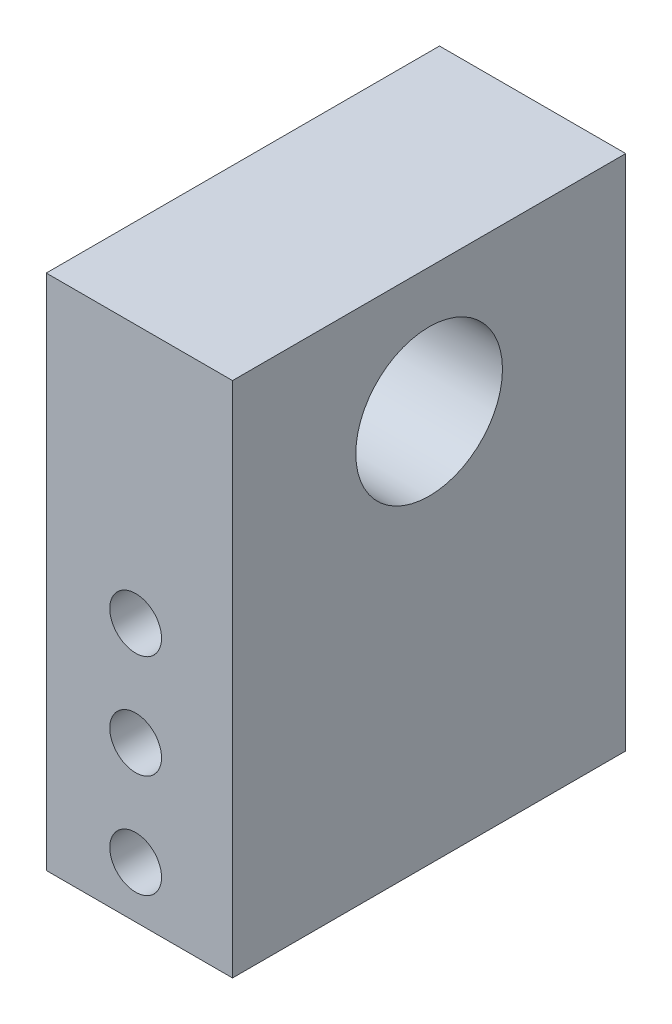
SolidWorks part; units mm, degrees
ref_plane "Front Plane" through (0, 0, 0) normal (0, 0, 1) x (1, 0, 0)
ref_plane "Top Plane" through (0, 0, 0) normal (0, 1, 0) x (1, 0, 0)
ref_plane "Right Plane" through (0, 0, 0) normal (1, 0, 0) x (0, 0, -1)
sketch "Sketch1" plane through (0, 0, 0) normal (0, 0, 1) x (1, 0, 0)
  line L1 (0, 0) -> (45.72, 0)
  line L2 (0, 0) -> (0, 76.2)
  line L3 (0, 76.2) -> (45.72, 76.2)
  line L4 (45.72, 0) -> (45.72, 76.2)
  dimension "D1" = 76.2
  dimension "D2" = 45.72
extrude "Boss-Extrude1" add sketch "Sketch1" along normal mid plane 96.52
sketch "Sketch2" plane through (0, 0, 48.26) normal (0, 0, 1) x (1, 0, 0)
  line L0 (0, 0) -> (45.72, 0) construction
  line L1 (45.72, 76.2) -> (0, 76.2) construction
  circle A0 centre (21.9441, 12.7) radius 6.35
  circle A1 centre (21.9441, 38.1) radius 6.35
  circle A2 centre (21.9441, 63.5) radius 6.35
  dimension "D1" = 12.7
  dimension "D2" = 12.7
  dimension "D3" = 12.7
  dimension "D4" = 25.4
  dimension "D5" = 25.4
  dimension "D6" = 12.7
  dimension "D7" = 12.7
extrude "Cut-Extrude1" cut sketch "Sketch2" against normal through all
sketch "Sketch3" plane through (0, 76.2, 0) normal (0, 1, 0) x (1, 0, 0)
  line L1 (0, 48.26) -> (45.72, 48.26)
  line L2 (0, 48.26) -> (0, -48.26)
  line L3 (0, -48.26) -> (45.72, -48.26)
  line L4 (45.72, 48.26) -> (45.72, -48.26)
extrude "Boss-Extrude2" add sketch "Sketch3" along normal blind 50.8
sketch "Sketch4" plane through (45.72, 0, 0) normal (1, 0, 0) x (0, 0, -1)
  line L0 (-48.26, 127) -> (48.26, 127) construction
  circle A0 centre (0, 96.3) radius 18
  dimension "D1" = 35.9999
  dimension "D2" = 30.7
extrude "Cut-Extrude2" cut sketch "Sketch4" against normal blind 40.64
sketch "Sketch5" plane through (5.08, 0, 0) normal (1, 0, 0) x (0, 0, -1)
  circle A0 centre (0, 96.3) radius 3
extrude "Cut-Extrude3" cut sketch "Sketch5" against normal through all
